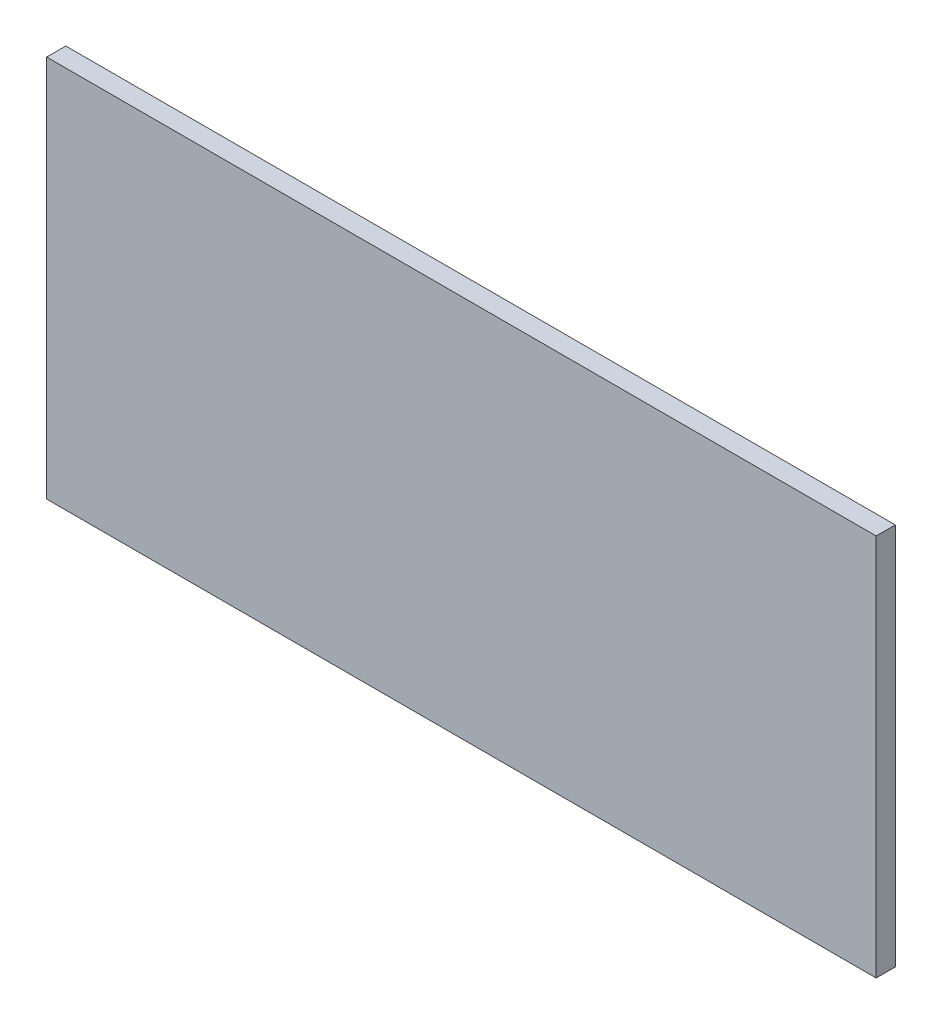
SolidWorks part; units mm, degrees
ref_plane "Front Plane" through (0, 0, 0) normal (0, 0, 1) x (1, 0, 0)
ref_plane "Top Plane" through (0, 0, 0) normal (0, 1, 0) x (1, 0, 0)
ref_plane "Right Plane" through (0, 0, 0) normal (1, 0, 0) x (0, 0, -1)
sketch "Sketch1" plane through (0, 0, 0) normal (0, 0, 1) x (1, 0, 0)
  line L0 (125.9407, 9.445) -> (125.9407, -9.555) construction
  line L1 (100.9407, 9.445) -> (150.9407, 9.445) construction
  line L2 (150.9407, -9.555) -> (100.9407, -9.555) construction
  line L3 (93.4407, 14.945) -> (93.4407, -15.055) construction
  line L5 (158.4407, -15.055) -> (158.4407, 14.945) construction
  line L6 (158.4407, 14.945) -> (93.4407, 14.945) construction
  line L7 (93.4407, 14.945) -> (93.4407, -15.055) construction
  line L8 (158.4407, -15.055) -> (93.4407, 14.945) construction
  line L9 (158.4407, 14.945) -> (93.4407, -15.055) construction
  line L12 (158.4407, 14.945) -> (93.4407, 14.945) construction
  line L13 (93.4407, -15.055) -> (93.4407, 14.945)
  line L14 (93.4407, 14.945) -> (158.4407, 14.945)
  line L15 (158.4407, 14.945) -> (158.4407, -15.055)
  line L16 (158.4407, -15.055) -> (93.4407, -15.055)
  point P6 (125.9407, -0.055)
  dimension "D1" = 65
  dimension "D2" = 30
extrude "Boss-Extrude1" add sketch "Sketch1" against normal blind 1.5
sketch "Sketch2" plane through (0, 0, -1.5) normal (0, 0, -1) x (-1, 0, 0)
  line L0 (-150.9407, 6.945) -> (-100.9407, 6.945) construction
  line L1 (-150.9407, -9.555) -> (-150.9407, 9.445) construction
  line L2 (-100.9407, -9.555) -> (-100.9407, 9.445) construction
  line L3 (-150.9407, -7.055) -> (-100.9407, -7.055) construction
  line L4 (-103.4407, 9.445) -> (-103.4407, -9.555) construction
  line L5 (-100.9407, 9.445) -> (-150.9407, 9.445) construction
  line L6 (-150.9407, -9.555) -> (-100.9407, -9.555) construction
  line L7 (-148.4407, 9.445) -> (-148.4407, -9.555) construction
  line L8 (-148.4407, 9.445) -> (-103.4407, 9.445)
  line L9 (-100.9407, 6.945) -> (-100.9407, -7.055)
  line L10 (-103.4407, -9.555) -> (-148.4407, -9.555)
  line L12 (-150.9407, -7.055) -> (-150.9407, 6.945)
  arc A0 (-150.9407, 6.945) -> (-148.4407, 9.445) centre (-148.4407, 6.945) cw
  arc A1 (-103.4407, 9.445) -> (-100.9407, 6.945) centre (-103.4407, 6.945) cw
  arc A2 (-103.4407, -9.555) -> (-100.9407, -7.055) centre (-103.4407, -7.055) ccw
  arc A3 (-148.4407, -9.555) -> (-150.9407, -7.055) centre (-148.4407, -7.055) cw
  dimension "D1" = 2.5
extrude "Boss-Extrude2" add sketch "Sketch2" along normal blind 1.5 separate body
